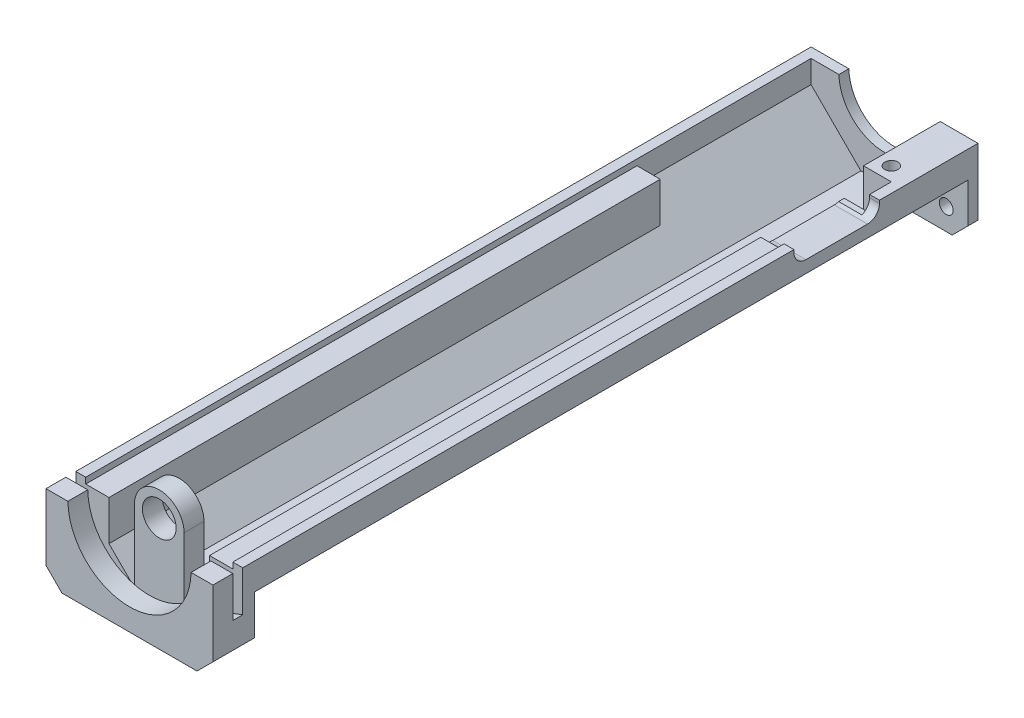
SolidWorks part; units mm, degrees
ref_plane "Front Plane" through (0, 0, 0) normal (0, 0, 1) x (1, 0, 0)
ref_plane "Top Plane" through (0, 0, 0) normal (0, 1, 0) x (1, 0, 0)
ref_plane "Right Plane" through (0, 0, 0) normal (1, 0, 0) x (0, 0, -1)
sketch "Sketch1" plane through (0, 0, 0) normal (0, 0, 1) x (1, 0, 0)
  line L0 (-21, -0.25) -> (21, -0.25)
  line L1 (-21, 21) -> (21, 21) construction
  line L2 (-21, 21) -> (-21, -21) construction
  line L3 (-21, -21) -> (21, -21) construction
  line L4 (21, 21) -> (21, -21) construction
  line L5 (-21, 21) -> (21, -21) construction
  line L6 (-21, -21) -> (21, 21) construction
  line L7 (21, -0.25) -> (21, -17)
  line L8 (21, -17) -> (17, -21)
  line L9 (17, -21) -> (-17, -21)
  line L10 (-17, -21) -> (-21, -17)
  line L11 (-21, -17) -> (-21, -0.25)
  point P0 (0, 0)
  dimension "D1" = 42
  dimension "D2" = 0.25
  dimension "D3" = 4
  dimension "D4" = 4
  dimension "D5" = 4
extrude "Boss-Extrude1" add sketch "Sketch1" along normal blind 192.5 contours L11 L0 L7 L8 L9 L10
ref_plane "Plane1" through (0, 0, 187.5) normal (0, 0, 1) x (1, 0, 0)
sketch "Sketch4" plane through (0, 0, 187.5) normal (0, 0, 1) x (1, 0, 0)
  line L0 (-18.5, -15.9645) -> (-15.9645, -18.5)
  line L1 (-15.9645, -18.5) -> (15.9645, -18.5)
  line L2 (15.9645, -18.5) -> (18.5, -15.9645)
  line L3 (18.5, -15.9645) -> (18.5, -2.75)
  line L5 (-18.5, -2.75) -> (-18.5, -15.9645)
  line L6 (-21, -17) -> (-17, -21)
  line L7 (-17, -21) -> (17, -21)
  line L8 (17, -21) -> (21, -17)
  line L9 (21, -17) -> (21, -0.25)
  line L10 (21, -0.25) -> (-21, -0.25)
  line L11 (-21, -0.25) -> (-21, -17)
  line L12 (-21, -17) -> (-17, -21) construction
  line L13 (-17, -21) -> (17, -21) construction
  line L14 (17, -21) -> (21, -17) construction
  line L15 (21, -17) -> (21, -0.25) construction
  line L16 (21, -0.25) -> (-21, -0.25) construction
  line L17 (-21, -0.25) -> (-21, -17) construction
  line L18 (18.5, -2.75) -> (-18.5, -2.75) construction
  line L19 (-18.5, -2.75) -> (-18.5, -0.25)
  line L20 (-18.5, -0.25) -> (18.5, -0.25)
  line L21 (18.5, -0.25) -> (18.5, -2.75)
  dimension "D1" = 0
  dimension "D2" = 2.5
extrude "Cut-Extrude3" cut sketch "Sketch4" against normal offset from surface (185 mm away) 2.5 up to face at (0, -12.75, 0)
sketch "Sketch2" plane through (0, 0, 0) normal (0, 0, -1) x (-1, 0, 0)
  line L0 (0, 0) -> (0, -21) construction
  line L1 (-17, -21) -> (17, -21) construction
  line L3 (15.5, 15.5) -> (-15.5, 15.5) construction
  line L4 (15.5, 15.5) -> (15.5, -15.5) construction
  line L5 (15.5, -15.5) -> (-15.5, -15.5) construction
  line L6 (-15.5, 15.5) -> (-15.5, -15.5) construction
  line L7 (15.5, 15.5) -> (-15.5, -15.5) construction
  line L8 (15.5, -15.5) -> (-15.5, 15.5) construction
  circle A0 centre (-15.5, -15.5) radius 1.75
  circle A1 centre (15.5, -15.5) radius 1.75
  dimension "D2" = 3.5
  dimension "D1" = 31
extrude "Cut-Extrude1" cut sketch "Sketch2" against normal blind 10
sketch "Sketch3" plane through (0, 0, 192.5) normal (0, 0, 1) x (1, 0, 0)
  circle A0 centre (0, 0) radius 15.5
  dimension "D1" = 31
extrude "Cut-Extrude2" cut sketch "Sketch3" against normal up to next
sketch "Sketch6" plane through (0, 0, 187.5) normal (0, 0, 1) x (1, 0, 0)
  line L0 (-23.48, 5.25) -> (-23.48, -5.25) construction
  line L1 (-25.1, 16.6) -> (25.1, 16.6) construction
  line L2 (-25.1, 16.6) -> (-25.1, -16.6) construction
  line L3 (-25.1, -16.6) -> (25.1, -16.6) construction
  line L4 (25.1, 16.6) -> (25.1, -16.6) construction
  line L5 (-25.1, 16.6) -> (25.1, -16.6) construction
  line L6 (-25.1, -16.6) -> (25.1, 16.6) construction
  line L7 (-21.0419, 8.75) -> (-5.3717, 14.5394) construction
  line L8 (-23.48, 0) -> (0, 0) construction
  line L9 (0, 0) -> (0, 16.6) construction
  line L10 (-21.0419, -8.75) -> (-5.3717, -14.5394) construction
  line L11 (21.0419, -8.75) -> (5.3717, -14.5394) construction
  line L12 (23.48, 5.25) -> (23.48, -5.25) construction
  line L13 (21.0419, 8.75) -> (5.3717, 14.5394) construction
  line L14 (-21.6033, 10.2696) -> (-5.9331, 16.059)
  line L15 (-25.1, 5.25) -> (-25.1, -5.25)
  line L16 (-21.6033, -10.2696) -> (-5.9331, -16.059)
  line L17 (21.6033, -10.2696) -> (5.9331, -16.059)
  line L18 (25.1, 5.25) -> (25.1, -5.25)
  line L19 (21.6033, 10.2696) -> (5.9331, 16.059)
  arc A0 (-5.3717, -14.5394) -> (5.3717, -14.5394) centre (0, 0) ccw construction
  arc A1 (-15.498, -0.25) -> (15.498, -0.25) centre (0, 0) ccw construction
  arc A2 (-23.48, 5.25) -> (-21.0419, 8.75) centre (-19.7488, 5.25) cw construction
  arc A3 (-23.48, -5.25) -> (-21.0419, -8.75) centre (-19.7488, -5.25) ccw construction
  arc A4 (23.48, -5.25) -> (21.0419, -8.75) centre (19.7488, -5.25) cw construction
  arc A5 (23.48, 5.25) -> (21.0419, 8.75) centre (19.7488, 5.25) ccw construction
  arc A6 (5.3717, 14.5394) -> (-5.3717, 14.5394) centre (0, 0) ccw construction
  arc A7 (5.9331, 16.059) -> (-5.9331, 16.059) centre (0, 0) ccw
  arc A8 (-25.1, 5.25) -> (-21.6033, 10.2696) centre (-19.7488, 5.25) cw
  arc A9 (-25.1, -5.25) -> (-21.6033, -10.2696) centre (-19.7488, -5.25) ccw
  arc A10 (-5.9331, -16.059) -> (5.9331, -16.059) centre (0, 0) ccw
  arc A11 (25.1, -5.25) -> (21.6033, -10.2696) centre (19.7488, -5.25) cw
  arc A12 (25.1, 5.25) -> (21.6033, 10.2696) centre (19.7488, 5.25) ccw
  point P0 (0, 0)
  point P14 (-23.48, 0)
  dimension "D1" = 50.2
  dimension "D2" = 33.2
  dimension "D3" = 1.62
  dimension "D4" = 10.5
  dimension "D5" = 17.5
  dimension "D6" = 1.62
extrude "Cut-Extrude4" cut sketch "Sketch6" against normal blind 2.5
ref_plane "Plane2" through (0, 0, 185) normal (0, 0, 1) x (1, 0, 0)
sketch "Sketch7" plane through (0, 0, 185) normal (0, 0, 1) x (1, 0, 0)
  line L1 (-6.25, 0) -> (-6.25, -18.5)
  line L2 (-6.25, -18.5) -> (6.25, -18.5)
  line L3 (6.25, -18.5) -> (6.25, 0)
  line L5 (15.9645, -18.5) -> (-15.9645, -18.5) construction
  arc A4 (-6.25, 0) -> (6.25, 0) centre (0, 0) cw
  circle A5 centre (0, 0) radius 4.25
  dimension "D2" = 6.25
  dimension "D1" = 8.5
extrude "Boss-Extrude3" add sketch "Sketch7" against normal blind 5 contours L3 A4 L1 L2
sketch "Sketch8" plane through (0, 0, 2.5) normal (0, 0, 1) x (1, 0, 0)
  circle A0 centre (0, 0) radius 11 construction
  circle A1 centre (0, 0) radius 11 construction
  circle A2 centre (0, 0) radius 11.5
  dimension "D1" = 0.5
extrude "Cut-Extrude5" cut sketch "Sketch8" against normal blind 10
sketch "Sketch10" plane through (0, 0, 185) normal (0, 0, 1) x (1, 0, 0)
  line L0 (-18.5, -1.75) -> (-18.5, -15.9645)
  line L1 (-18.5, -15.9645) -> (-18.5, -0.25) construction
  line L2 (-18.5, -15.9645) -> (-15.9645, -18.5)
  line L3 (-15.9645, -18.5) -> (-12.65, -18.5)
  line L4 (15.9645, -18.5) -> (-15.9645, -18.5) construction
  line L5 (-12.65, -18.5) -> (-12.65, -1.75)
  line L6 (-18.5, -1.75) -> (-12.65, -1.75)
  line L8 (-17.5, -1.5) -> (-12.0571, -1.5) construction
  dimension "D1" = 0.25
  dimension "D2" = 0.5
extrude "Boss-Extrude4" add sketch "Sketch10" against normal offset from surface (138.7 mm away) 7 contours L6 L5 L3 L2 L0
mirror "Mirror1" about plane through (0, 0, 0) normal (1, 0, 0) of "Boss-Extrude4"
sketch "Sketch11" plane through (0, 0, 185) normal (0, 0, 1) x (1, 0, 0)
  circle A0 centre (0, 0) radius 4.25
  dimension "D1" = 8.5
extrude "Cut-Extrude6" cut sketch "Sketch11" against normal blind 10
sketch "Sketch12" plane through (0, 0, 2.5) normal (0, 0, 1) x (1, 0, 0)
  line L0 (-18.5, -15.9645) -> (-18.5, -0.25) construction
  line L1 (15.9645, -18.5) -> (-15.9645, -18.5) construction
  line L2 (-15.9645, -18.5) -> (-18.5, -15.9645) construction
  line L3 (-18.5, -15.9645) -> (-18.5, -5.9645)
  line L4 (-5.9645, -18.5) -> (-15.9645, -18.5)
  line L5 (-15.9645, -18.5) -> (-18.5, -15.9645)
  line L6 (-18.5, -5.9645) -> (-5.9645, -18.5)
  line L7 (-18.5, -0.25) -> (-18.5, -15.9645) construction
  line L8 (0, 0) -> (0, -18.5) construction
  line L9 (18.5, -5.9645) -> (5.9645, -18.5)
  line L10 (15.9645, -18.5) -> (18.5, -15.9645)
  line L11 (5.9645, -18.5) -> (15.9645, -18.5)
  line L12 (18.5, -15.9645) -> (18.5, -5.9645)
  dimension "D1" = 10
extrude "Boss-Extrude5" add sketch "Sketch12" along normal up to surface (182.5 mm away) up to face at (17.4738, -8.7637, 185)
ref_plane "Plane3" through (0, 0, 2.5) normal (0, 0, 1) x (1, 0, 0)
sketch "Sketch14" plane through (0, 0, 2.5) normal (0, 0, 1) x (1, 0, 0)
  line L1 (-5.9645, -18.5) -> (-18.5, -5.9645) construction
  line L2 (-7.7322, -20.2678) -> (-20.2678, -7.7322) construction
  line L3 (-5.9645, -18.5) -> (-18.5, -5.9645) construction
  line L4 (-21, -17) -> (-21, -0.25) construction
  line L5 (-7, -21) -> (-21, -7)
  line L6 (17, -21) -> (-17, -21) construction
  line L7 (-17, -21) -> (-21, -17) construction
  line L8 (-17, -21) -> (-21, -17)
  line L9 (-21, -7) -> (-21, -17)
  line L10 (-7, -21) -> (-17, -21)
  line L11 (0, 0) -> (0, -21) construction
  line L12 (7, -21) -> (17, -21)
  line L13 (21, -7) -> (21, -17)
  line L14 (17, -21) -> (21, -17)
  line L15 (7, -21) -> (21, -7)
  dimension "D1" = 2.5
extrude "Cut-Extrude7" cut sketch "Sketch14" along normal offset from surface (179.5 mm away) 3 up to face at (0, -7.9343, 185)
sketch "Sketch15" plane through (0, 0, 2.5) normal (0, 0, 1) x (1, 0, 0)
  circle A0 centre (15.5, -15.5) radius 1.75 construction
  circle A1 centre (-15.5, -15.5) radius 1.75 construction
  circle A2 centre (15.5, -15.5) radius 1.75 construction
  circle A3 centre (-15.5, -15.5) radius 1.75 construction
  circle A4 centre (15.5, -15.5) radius 3.75
  circle A5 centre (-15.5, -15.5) radius 3.75
  dimension "D1" = 2
ref_plane "Plane4" through (0, 0, 17.5) normal (0, 0, 1) x (1, 0, 0)
sketch "Sketch16" plane through (0, 0, 17.5) normal (0, 0, 1) x (1, 0, 0)
  line L0 (-7, -21) -> (-21, -7) construction
  line L1 (0, 0) -> (0, -21) construction
  line L2 (-14.15, -21) -> (14.15, -21) construction
  circle A0 centre (-15.5, -15.5) radius 2.1213
  circle A1 centre (15.5, -15.5) radius 2.1213
loft "Cut-Loft1" cut section "Sketch15" section "Sketch16" start constraint normal to profile start tangent length 1 connector at (-17.4754, -12.3125, 2.5) connector at (-17.2146, -14.251, 17.5)
mirror "Mirror2" about plane through (0, 0, 0) normal (1, 0, 0) of "Cut-Loft1"
sketch "Sketch17" plane through (0, 0, 46.3) normal (0, 0, -1) x (-1, 0, 0)
  line L0 (-18.5, -1.75) -> (-18.5, -5.9645) construction
  line L1 (-12.65, -11.8145) -> (-12.65, -1.75) construction
  line L2 (-18.5, -5.9645) -> (-12.65, -11.8145) construction
  line L3 (-18.5, -3.75) -> (-18.5, -5.9645)
  line L4 (-12.65, -11.8145) -> (-12.65, -3.75)
  line L5 (-18.5, -5.9645) -> (-12.65, -11.8145)
  line L6 (-12.65, -3.75) -> (-18.5, -3.75)
  line L8 (-18.5, -1.75) -> (-12.65, -1.75) construction
  dimension "D1" = 2
extrude "Boss-Extrude6" add sketch "Sketch17" along normal blind 21
sketch "Sketch19" plane through (21, 0, 0) normal (1, 0, 0) x (0, 0, -1)
  line L0 (-46.3, 14.55) -> (-46.3, -0.95)
  line L1 (-43.3, -3.95) -> (-27.8, -3.95)
  line L2 (-24.8, -0.95) -> (-24.8, 14.55)
  line L3 (-27.8, 17.55) -> (-43.3, 17.55)
  line L4 (-45.8, 14.55) -> (-45.8, -0.95)
  line L5 (-43.3, -3.45) -> (-27.8, -3.45)
  line L6 (-25.3, -0.95) -> (-25.3, 14.55)
  line L7 (-27.8, 17.05) -> (-43.3, 17.05)
  line L8 (-45.8, 14.55) -> (-45.8, -0.95) construction
  line L9 (-43.3, -3.45) -> (-27.8, -3.45) construction
  line L10 (-25.3, -0.95) -> (-25.3, 14.55) construction
  line L11 (-27.8, 17.05) -> (-43.3, 17.05) construction
  arc A0 (-43.3, 17.55) -> (-46.3, 14.55) centre (-43.3, 14.55) ccw
  arc A1 (-46.3, -0.95) -> (-43.3, -3.95) centre (-43.3, -0.95) ccw
  arc A2 (-27.8, -3.95) -> (-24.8, -0.95) centre (-27.8, -0.95) ccw
  arc A3 (-24.8, 14.55) -> (-27.8, 17.55) centre (-27.8, 14.55) ccw
  arc A4 (-43.3, 17.05) -> (-45.8, 14.55) centre (-43.3, 14.55) ccw
  arc A5 (-45.8, -0.95) -> (-43.3, -3.45) centre (-43.3, -0.95) ccw
  arc A6 (-27.8, -3.45) -> (-25.3, -0.95) centre (-27.8, -0.95) ccw
  arc A7 (-25.3, 14.55) -> (-27.8, 17.05) centre (-27.8, 14.55) ccw
  arc A8 (-43.3, 17.05) -> (-45.8, 14.55) centre (-43.3, 14.55) ccw construction
  arc A9 (-45.8, -0.95) -> (-43.3, -3.45) centre (-43.3, -0.95) ccw construction
  arc A10 (-27.8, -3.45) -> (-25.3, -0.95) centre (-27.8, -0.95) ccw construction
  arc A11 (-25.3, 14.55) -> (-27.8, 17.05) centre (-27.8, 14.55) ccw construction
  dimension "D1" = 0
  dimension "D2" = 0.5
extrude "Cut-Extrude8" cut sketch "Sketch19" against normal blind 21
ref_plane "Plane5" through (11.4973, 0.25, 19.3) normal (0, 0, -1) x (-1, 0, 0)
sketch "Sketch21" plane through (0, -0.25, 0) normal (0, 1, 0) x (1, 0, 0)
  line L4 (18.5, -19.3) -> (18.5, -2.5)
  line L5 (18.5, -2.5) -> (11.4973, -2.5)
  line L6 (11.4973, -2.5) -> (11.4973, -19.3)
  line L7 (11.4973, -19.3) -> (18.5, -19.3)
  line L8 (18.5, -19.3) -> (18.5, -2.5)
  line L9 (18.5, -2.5) -> (11.4973, -2.5)
  line L10 (11.4973, -2.5) -> (11.4973, -19.3)
  line L11 (11.4973, -19.3) -> (18.5, -19.3)
  dimension "D1" = 0
extrude "Boss-Extrude7" add sketch "Sketch21" against normal up to surface (12.7172 mm away) up to face at (10.8411, -13.6233, 98.2)
sketch "Sketch22" plane through (0, -0.25, 0) normal (0, 1, 0) x (1, 0, 0)
  line L0 (14.9986, -19.3) -> (14.9986, 0) construction
  line L1 (11.4973, -19.3) -> (18.5, -19.3) construction
  line L2 (11.4973, 0) -> (21, 0) construction
  circle A0 centre (14.9986, -15.8) radius 1.65
  dimension "D1" = 3.3
  dimension "D2" = 3.5
extrude "Cut-Extrude9" cut sketch "Sketch22" against normal through all
ref_plane "Plane6" through (0, -7, 0) normal (0, 1, 0) x (1, 0, 0)
sketch "Sketch23" plane through (0, -7, 0) normal (0, 1, 0) x (1, 0, 0)
  circle A1 centre (14.9986, -15.8) radius 3
  dimension "D1" = 6
extrude "Cut-Extrude10" cut sketch "Sketch23" against normal through all
